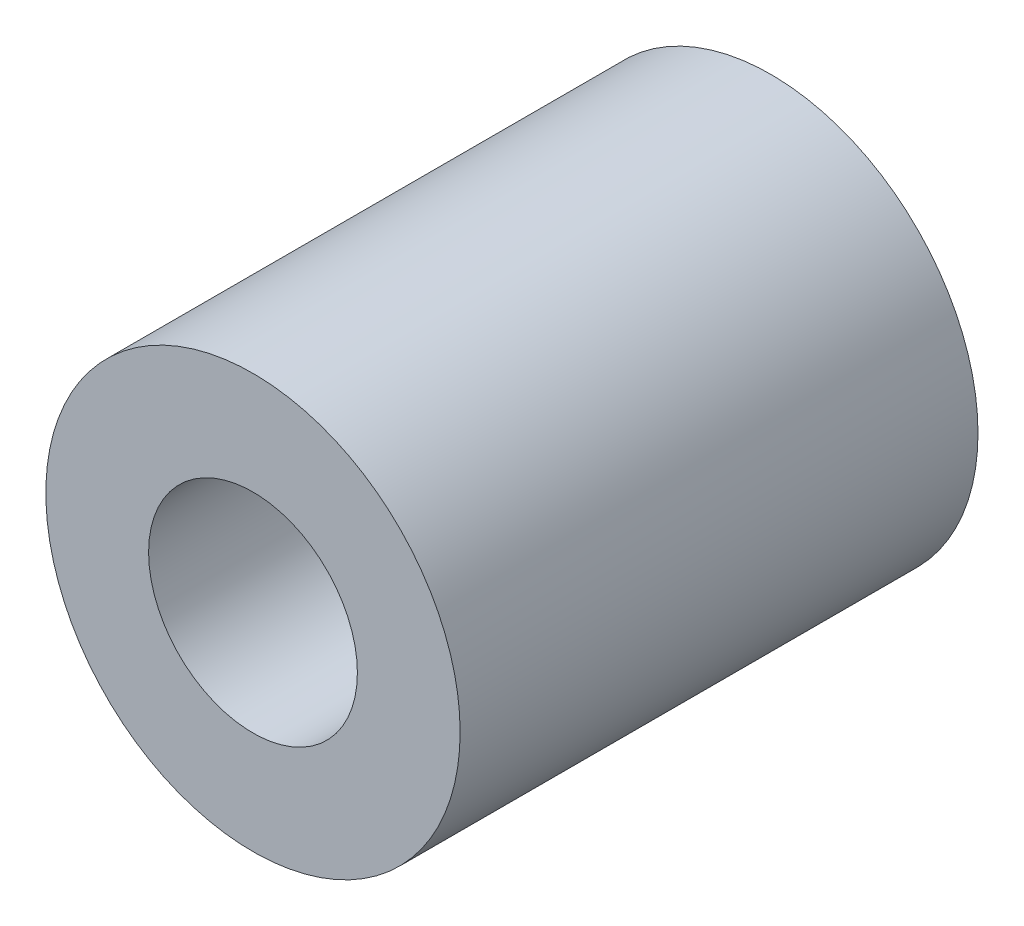
SolidWorks part; units mm, degrees
ref_plane "Front Plane" through (0, 0, 0) normal (0, 0, 1) x (1, 0, 0)
ref_plane "Top Plane" through (0, 0, 0) normal (0, 1, 0) x (1, 0, 0)
ref_plane "Right Plane" through (0, 0, 0) normal (1, 0, 0) x (0, 0, -1)
sketch "Sketch1" plane through (0, 0, 0) normal (0, 0, 1) x (1, 0, 0)
  circle A0 centre (0, 0) radius 6.35
  circle A1 centre (0, 0) radius 3.2004
  dimension "OD" = 12.7
  dimension "ID" = 6.4008
extrude "Extrude1" add sketch "Sketch1" along normal mid plane 15.875
sketch "Sketch2" plane through (0, 0, 0) normal (1, 0, 0) x (0, 0, -1)
  line L0 (-7.9375, -3.2004) -> (7.9375, -3.2004) construction
  line L3 (7.9375, 3.2004) -> (-7.9375, 3.2004) construction
  line L5 (-7.9375, -3.2004) -> (7.9375, -3.2004)
  line L6 (7.9375, 3.2004) -> (-7.9375, 3.2004)
sketch "Sketch4" plane through (0, 0, 7.9375) normal (0, 0, 1) x (1, 0, 0)
  line L0 (0, 0) -> (-2.263, 2.263)
  line L1 (0, -5.2388) -> (0, 5.2388) construction
  circle A0 centre (0, 0) radius 3.2004 construction
  dimension "D1" = 45
